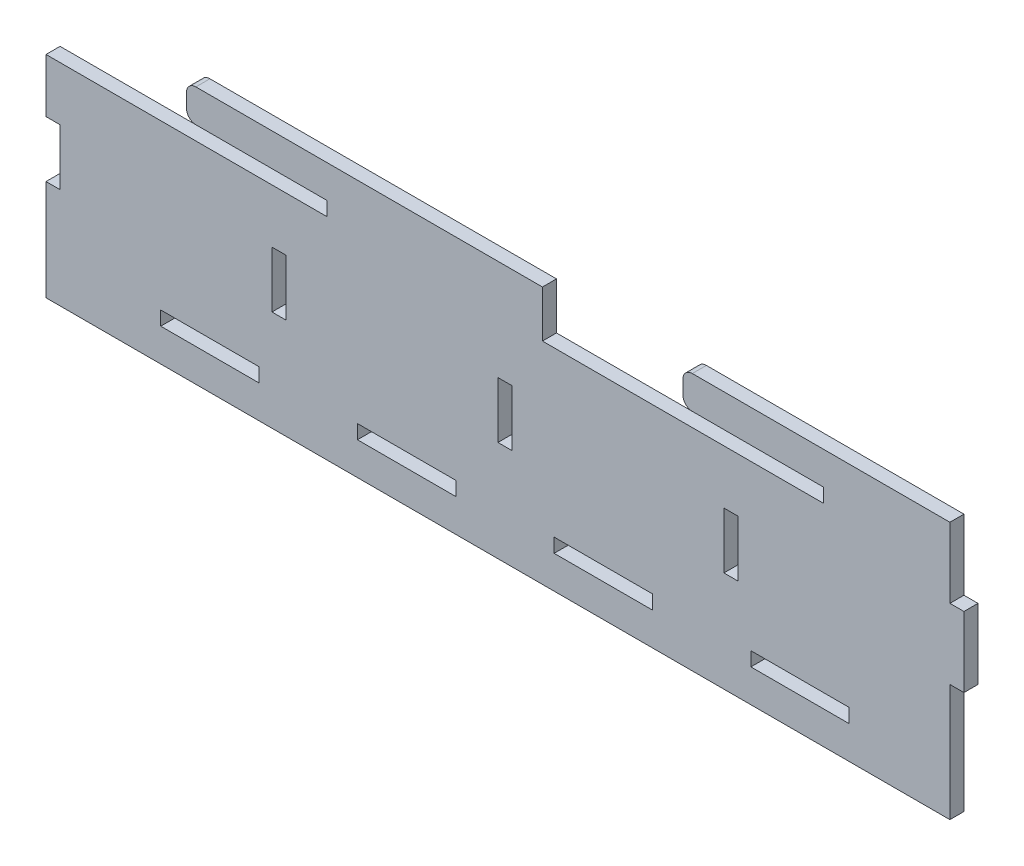
SolidWorks part; units mm, degrees
ref_plane "Front Plane" through (0, 0, 0) normal (0, 0, 1) x (1, 0, 0)
ref_plane "Top Plane" through (0, 0, 0) normal (0, 1, 0) x (1, 0, 0)
ref_plane "Right Plane" through (0, 0, 0) normal (1, 0, 0) x (0, 0, -1)
sketch "Sketch1" plane through (0, 0, 0) normal (0, 0, 1) x (1, 0, 0)
  line L0 (-102.4545, -7.25) -> (-99.4545, -7.25)
  line L1 (-102.4545, -28.75) -> (93.5455, -28.75)
  line L2 (-102.4545, -28.75) -> (-102.4545, 26.25)
  line L3 (-102.4545, 26.25) -> (93.5455, 26.25)
  line L4 (93.5455, -28.75) -> (93.5455, 26.25)
  line L5 (-102.4545, -28.75) -> (93.5455, 26.25) construction
  line L6 (-102.4545, 26.25) -> (93.5455, -28.75) construction
  line L7 (-99.4545, -7.25) -> (-99.4545, 4.75)
  line L8 (-99.4545, 4.75) -> (-102.4545, 4.75)
  line L9 (90.5455, -28.75) -> (90.5455, -3.75)
  line L10 (90.5455, -3.75) -> (93.5455, -3.75)
  line L11 (90.5455, 26.25) -> (90.5455, 11.25)
  line L12 (90.5455, 11.25) -> (93.5455, 11.25)
  line L13 (-72.4545, 26.25) -> (-72.4545, 19.25)
  line L14 (-54.2045, -7.25) -> (-51.2045, -7.25)
  line L15 (-54.2045, -7.25) -> (-54.2045, 4.75)
  line L16 (-54.2045, 4.75) -> (-51.2045, 4.75)
  line L17 (-51.2045, -7.25) -> (-51.2045, 4.75)
  line L18 (-54.2045, -7.25) -> (-51.2045, 4.75) construction
  line L19 (-54.2045, 4.75) -> (-51.2045, -7.25) construction
  line L20 (-5.9545, -7.25) -> (-2.9545, -7.25)
  line L21 (-5.9545, -7.25) -> (-5.9545, 4.75)
  line L22 (-5.9545, 4.75) -> (-2.9545, 4.75)
  line L23 (-2.9545, -7.25) -> (-2.9545, 4.75)
  line L24 (-5.9545, -7.25) -> (-2.9545, 4.75) construction
  line L25 (-5.9545, 4.75) -> (-2.9545, -7.25) construction
  line L26 (45.2955, -7.25) -> (42.2955, -7.25)
  line L27 (45.2955, -7.25) -> (45.2955, 4.75)
  line L28 (45.2955, 4.75) -> (42.2955, 4.75)
  line L29 (42.2955, -7.25) -> (42.2955, 4.75)
  line L30 (45.2955, -7.25) -> (42.2955, 4.75) construction
  line L31 (45.2955, 4.75) -> (42.2955, -7.25) construction
  line L32 (-72.4545, 19.25) -> (-42.4545, 19.25)
  line L33 (-42.4545, 19.25) -> (-42.4545, 16.25)
  line L34 (-42.4545, 16.25) -> (-102.4545, 16.25)
  line L35 (3.5455, 26.25) -> (3.5455, 16.25)
  line L36 (3.5455, 16.25) -> (63.5455, 16.25)
  line L37 (63.5455, 16.25) -> (63.5455, 19.25)
  line L38 (63.5455, 19.25) -> (33.5455, 19.25)
  line L39 (33.5455, 19.25) -> (33.5455, 26.25)
  line L41 (-77.9545, -21.75) -> (-56.9545, -21.75)
  line L42 (-77.9545, -21.75) -> (-77.9545, -18.75)
  line L43 (-77.9545, -18.75) -> (-56.9545, -18.75)
  line L44 (-56.9545, -21.75) -> (-56.9545, -18.75)
  line L45 (-77.9545, -21.75) -> (-56.9545, -18.75) construction
  line L46 (-77.9545, -18.75) -> (-56.9545, -21.75) construction
  line L47 (27.0455, -21.75) -> (6.0455, -21.75)
  line L48 (27.0455, -21.75) -> (27.0455, -18.75)
  line L49 (27.0455, -18.75) -> (6.0455, -18.75)
  line L50 (6.0455, -21.75) -> (6.0455, -18.75)
  line L51 (27.0455, -21.75) -> (6.0455, -18.75) construction
  line L52 (27.0455, -18.75) -> (6.0455, -21.75) construction
  line L53 (-14.9545, -21.75) -> (-35.9545, -21.75)
  line L54 (-14.9545, -21.75) -> (-14.9545, -18.75)
  line L55 (-14.9545, -18.75) -> (-35.9545, -18.75)
  line L56 (-35.9545, -21.75) -> (-35.9545, -18.75)
  line L57 (-14.9545, -21.75) -> (-35.9545, -18.75) construction
  line L58 (-14.9545, -18.75) -> (-35.9545, -21.75) construction
  line L71 (48.0455, -21.75) -> (69.0455, -21.75)
  line L72 (48.0455, -21.75) -> (48.0455, -18.75)
  line L73 (48.0455, -18.75) -> (69.0455, -18.75)
  line L74 (69.0455, -21.75) -> (69.0455, -18.75)
  line L75 (48.0455, -21.75) -> (69.0455, -18.75) construction
  line L76 (48.0455, -18.75) -> (69.0455, -21.75) construction
  point P0 (-67.4545, -20.25)
  point P43 (16.5455, -20.25)
  point P48 (-25.4545, -20.25)
  point P63 (58.5455, -20.25)
  dimension "D1" = 196
  dimension "D2" = 55
  dimension "D3" = 12
  dimension "D4" = 21.5
  dimension "D5" = 3
  dimension "D6" = 3
  dimension "D7" = 25
  dimension "D8" = 15
  dimension "D9" = 12
  dimension "D10" = 3
  dimension "D11" = 24.5
  dimension "D12" = 45.25
  dimension "D13" = 12
  dimension "D14" = 3
  dimension "D15" = 45.25
  dimension "D16" = 3
  dimension "D17" = 12
  dimension "D18" = 45.25
  dimension "D19" = 21
  dimension "D20" = 30
  dimension "D21" = 30
  dimension "D22" = 3
  dimension "D23" = 7
  dimension "D24" = 30
  dimension "D25" = 30
  dimension "D26" = 30
  dimension "D27" = 3
  dimension "D28" = 7
  dimension "D29" = 0
  dimension "D30" = 0
  dimension "D31" = 11.5
  dimension "D32" = 21
  dimension "D33" = 21
  dimension "D34" = 21
  dimension "D35" = 21
  dimension "D36" = 21
  dimension "D37" = 21
  dimension "D38" = 7
  dimension "D39" = 3
  dimension "D40" = 3
  dimension "D41" = 7
  dimension "D42" = 3
  dimension "D43" = 7
  dimension "D44" = 3
  dimension "D45" = 7
  dimension "D46" = 46
  dimension "D47" = 15
  dimension "D48" = 11.5
  dimension "D49" = 24.5
  dimension "D50" = 10
extrude "Boss-Extrude1" add sketch "Sketch1" along normal blind 3 contours L12 L11 L3 L2 L8 L7 L0 L1 L9 L10 L4 region at (-100.9545, -9.2857, 0)
fillet "Fillet1" radius 2 4 edges at (33.5455, 19.25, 1.5) (33.5455, 26.25, 1.5) (-72.4545, 19.25, 1.5) (-72.4545, 26.25, 1.5)
